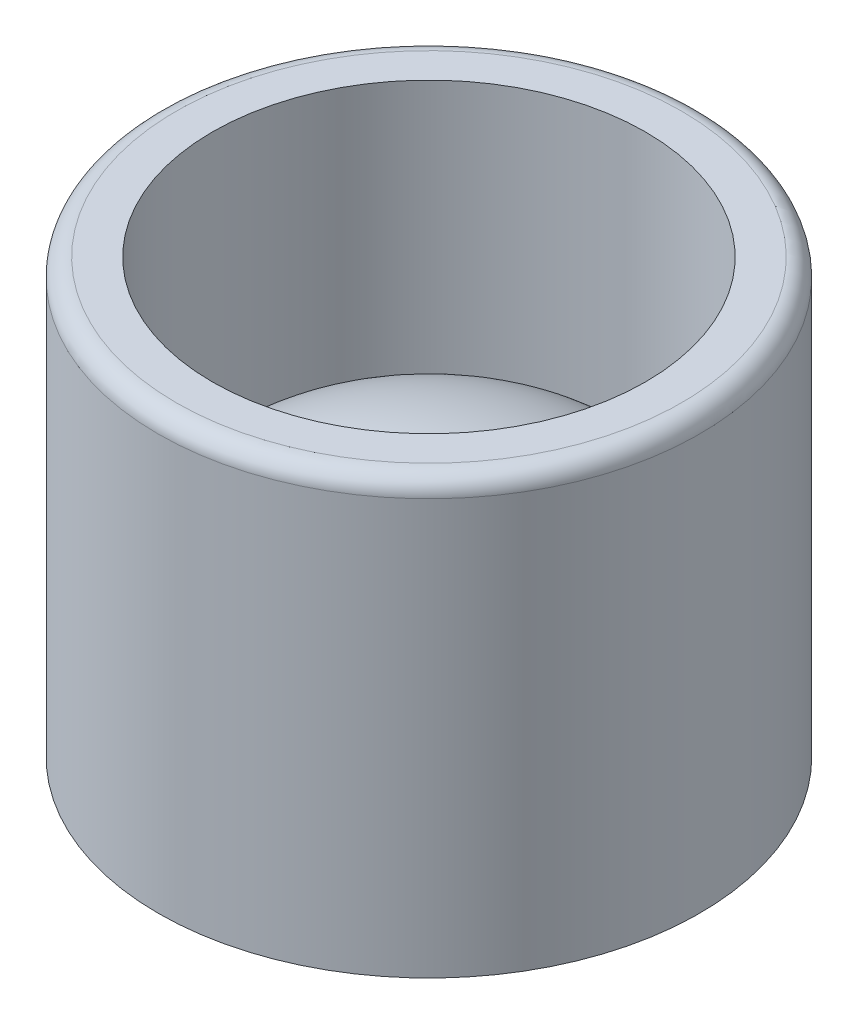
SolidWorks part; units mm, degrees
material "1060 Alloy"
ref_plane "Front Plane" through (0, 0, 0) normal (0, 0, 1) x (1, 0, 0)
ref_plane "Top Plane" through (0, 0, 0) normal (0, 1, 0) x (1, 0, 0)
ref_plane "Right Plane" through (0, 0, 0) normal (1, 0, 0) x (0, 0, -1)
sketch "Sketch2" plane through (0, 0, 0) normal (0, 1, 0) x (1, 0, 0)
  circle A0 centre (0, 0) radius 7.5
  dimension "D1" = 15
extrude "Boss-Extrude1" add sketch "Sketch2" along normal blind 12
sketch "Sketch3" plane through (0, 12, 0) normal (0, 1, 0) x (1, 0, 0)
  circle A0 centre (0, 0) radius 6
extrude "Cut-Extrude1" cut sketch "Sketch3" against normal blind 8
dome "Dome1" faces to dome 1 distance 3 reverse direction no elliptical dome yes face at (0, 4, 6) parameters "D1"=3
fillet "Fillet1" radius 0.5 1 edges at (0, 12, 7.5)
